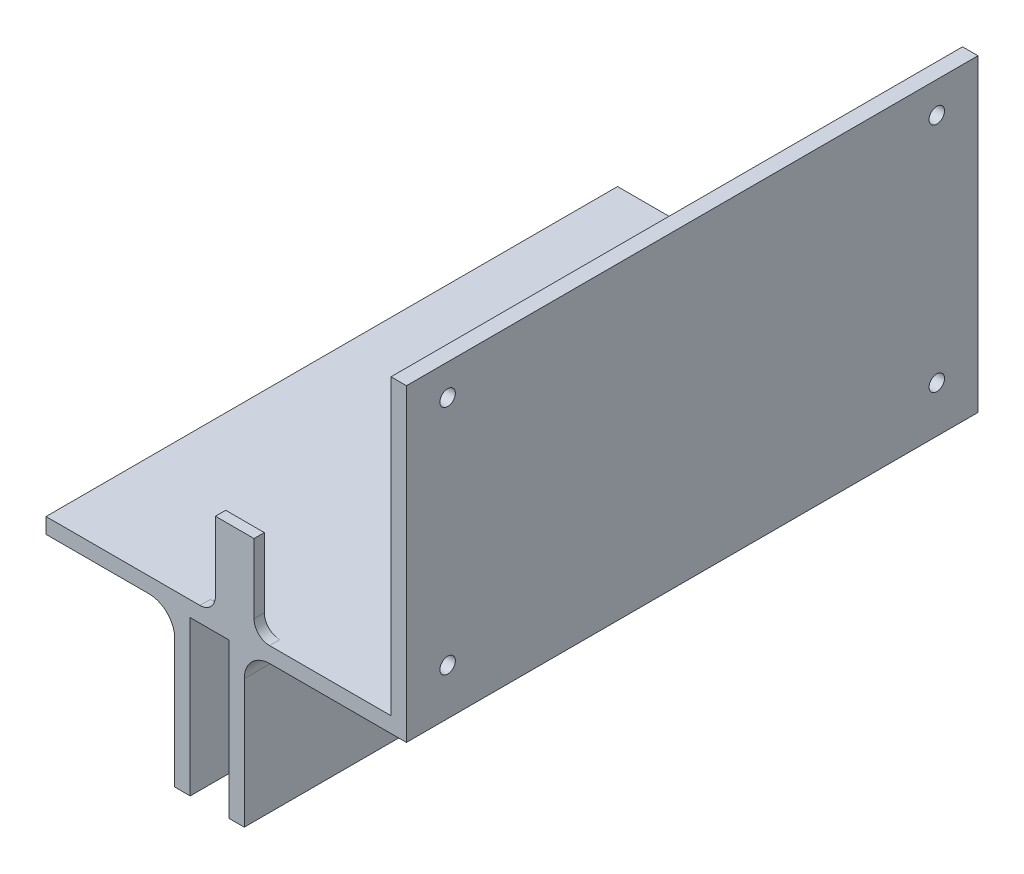
SolidWorks part; units mm, degrees
ref_plane "Front Plane" through (0, 0, 0) normal (0, 0, 1) x (1, 0, 0)
ref_plane "Top Plane" through (0, 0, 0) normal (0, 1, 0) x (1, 0, 0)
ref_plane "Right Plane" through (0, 0, 0) normal (1, 0, 0) x (0, 0, -1)
sketch "Sketch2" plane through (0, 0, 0) normal (0, 0, 1) x (1, 0, 0)
  line L0 (18.505, 30) -> (45, 30)
  line L1 (0, 0) -> (3, 0)
  line L2 (0, 0) -> (0, 25)
  line L4 (3, 0) -> (3, 30)
  line L5 (0, 33) -> (42, 33)
  line L7 (3, 30) -> (10.505, 30)
  line L10 (45, 30) -> (45, 90)
  line L11 (45, 90) -> (42, 90)
  line L12 (42, 33) -> (42, 90)
  line L14 (10.505, 30) -> (10.505, 0)
  line L15 (10.505, 0) -> (13.505, 0)
  line L16 (13.505, 25) -> (13.505, 0)
  line L18 (0, 33) -> (-25, 33)
  line L20 (-5, 30) -> (-25, 30)
  line L21 (-25, 33) -> (-25, 30)
  arc A0 (18.505, 30) -> (13.505, 25) centre (18.505, 25) ccw
  arc A1 (0, 25) -> (-5, 30) centre (-5, 25) ccw
  point P20 (0, 30)
  dimension "D10" = 5
  dimension "D1" = 7.505
  dimension "D2" = 3
  dimension "D3" = 3
  dimension "D4" = 3
  dimension "D5" = 3
  dimension "D6" = 60
  dimension "D7" = 45
  dimension "D8" = 3
  dimension "D9" = 25
  dimension "D11" = 25
  dimension "D12" = 25
extrude "Boss-Extrude1" add sketch "Sketch2" along normal blind 111
sketch "Sketch3" plane through (0, 0, 0) normal (-1, 0, 0) x (0, 0, 1)
  line L0 (55.5, 0) -> (55.5, 25) construction
  line L1 (111, 0) -> (0, 0) construction
  line L2 (111, 25) -> (0, 25) construction
  line L3 (111, 30) -> (0, 30) construction
  circle A0 centre (29.25, 20.25) radius 2.75
  circle A1 centre (81.75, 20.25) radius 2.75
  dimension "D1" = 5.5
  dimension "D2" = 26.25
  dimension "D3" = 9.75
extrude "Cut-Extrude1" cut sketch "Sketch3" against normal through all
sketch "Sketch5" plane through (42, 0, 0) normal (-1, 0, 0) x (0, 0, 1)
  line L0 (55.5, 33) -> (55.5, 90) construction
  line L1 (111, 33) -> (0, 33) construction
  line L2 (111, 90) -> (0, 90) construction
  line L3 (0, 61.5) -> (111, 61.5) construction
  line L4 (0, 90) -> (0, 33) construction
  line L5 (111, 90) -> (111, 33) construction
  circle A0 centre (8, 39) radius 1.5
  circle A1 centre (103, 39) radius 1.5
  circle A2 centre (103, 84) radius 1.5
  circle A3 centre (8, 84) radius 1.5
  dimension "D1" = 3
  dimension "D2" = 47.5
  dimension "D3" = 22.5
extrude "Cut-Extrude2" cut sketch "Sketch5" against normal through all
sketch "Sketch7" plane through (0, 0, 0) normal (0, 0, -1) x (-1, 0, 0)
  line L1 (-18.505, 30) -> (6.3663, 30)
  line L2 (-18.505, 30) -> (-18.505, 0)
  line L3 (-18.505, 0) -> (6.3663, 0)
  line L4 (6.3663, 30) -> (6.3663, 0)
extrude "Cut-Extrude5" cut sketch "Sketch7" against normal blind 19.5 contours L2 L3 L4 L1
fillet "Fillet1" radius 19.5 2 edges at (-1, 30, 19.5) (14.505, 30, 19.5)
sketch "Sketch8" plane through (0, 33, 0) normal (0, 1, 0) x (1, 0, 0)
  line L0 (42, 0) -> (-25, 0) construction
  line L1 (7.8995, 0) -> (15.4012, 0)
  line L2 (7.8995, 0) -> (7.8995, -2)
  line L3 (7.8995, -2) -> (15.4012, -2)
  line L4 (15.4012, 0) -> (15.4012, -2)
  dimension "D1" = 2
extrude "Boss-Extrude2" add sketch "Sketch8" along normal blind 16.5
fillet "Fillet2" radius 3 2 edges at (15.4012, 33, 1) (7.8995, 33, 1)
ref_plane "Plane1" through (0, 0, 55.5) normal (0, 0, 1) x (1, 0, 0)
mirror "Mirror1" about plane through (0, 0, 55.5) normal (0, 0, 1) of "Boss-Extrude2", "Fillet2"
